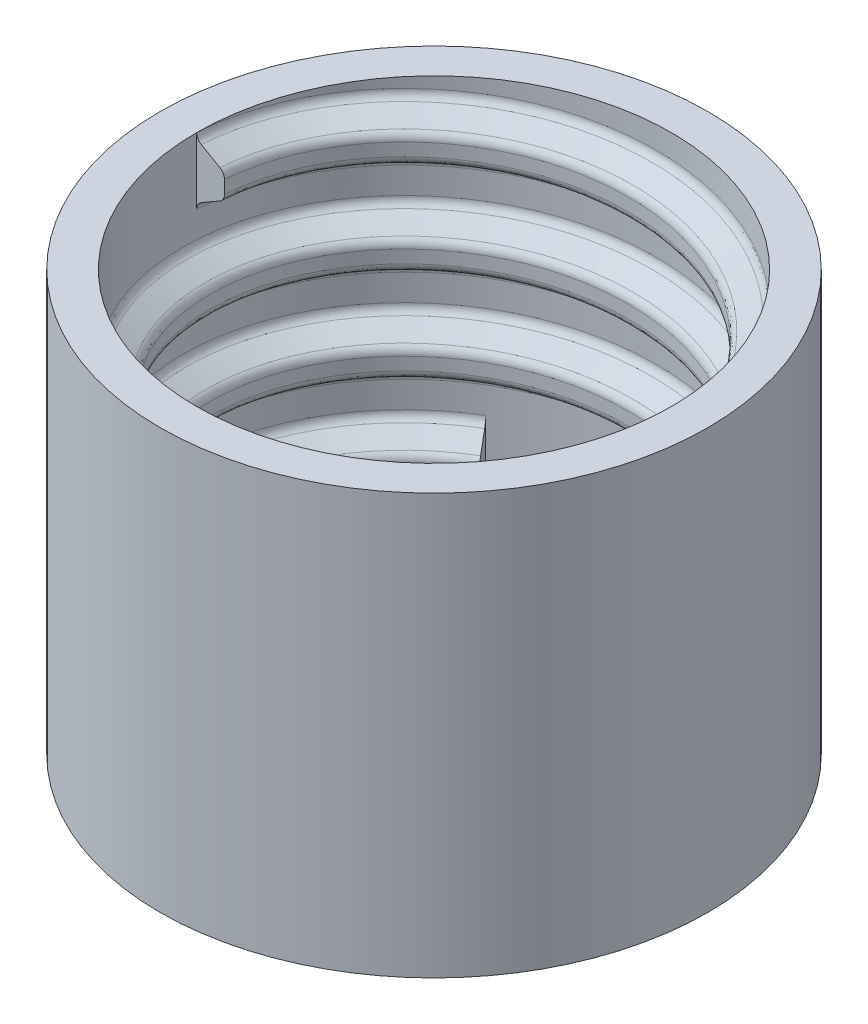
SolidWorks part; units mm, degrees
ref_plane "Front Plane" through (0, 0, 0) normal (0, 0, 1) x (1, 0, 0)
ref_plane "Top Plane" through (0, 0, 0) normal (0, 1, 0) x (1, 0, 0)
ref_plane "Right Plane" through (0, 0, 0) normal (1, 0, 0) x (0, 0, -1)
sketch "Sketch1" plane through (0, 0, 0) normal (0, 1, 0) x (1, 0, 0)
  circle A0 centre (0, 0) radius 15
extrude "Boss-Extrude1" add sketch "Sketch1" along normal blind 20 contours A0
sketch "Sketch2" plane through (0, 20, 0) normal (0, 1, 0) x (1, 0, 0)
  circle A0 centre (0, 0) radius 13
sketch "Sketch10" plane through (0, 20, 0) normal (0, 1, 0) x (1, 0, 0)
  circle A0 centre (0, 0) radius 13
extrude "Cut-Extrude2" cut sketch "Sketch10" against normal blind 20
thread "Thread1" pitch 5.08 method extrude profile "Thread Profile2" start angle 0, offset 0, length 16, pitch 5.08, diameter 26
ref_plane "Plane2" through (-13, 20, 0) normal (0, 0, -1) x (1, 0, 0)
sketch "Thread Profile2" plane through (-13, 20, 0) normal (0, 0, -1) x (1, 0, 0)
  line L0 (0, 0) -> (0, 5.08) construction
  line L1 (0, 0) -> (0, 3.6346)
  line L2 (0.508, 3.6346) -> (1.524, 3.6346) construction
  line L3 (1.524, 2.1681) -> (1.524, 1.4665)
  line L4 (1.27, 2.6081) -> (0.254, 3.1946)
  line L5 (1.27, 1.0265) -> (0.254, 0.4399)
  line L6 (0.508, 0) -> (1.524, 0) construction
  arc A0 (0.254, 3.1946) -> (0, 3.6346) centre (0.508, 3.6346) cw
  arc A1 (0.254, 0.4399) -> (0, 0) centre (0.508, 0) ccw
  arc A2 (1.524, 1.4665) -> (1.27, 1.0265) centre (1.016, 1.4665) cw
  arc A3 (1.524, 2.1681) -> (1.27, 2.6081) centre (1.016, 2.1681) ccw
  point P10 (1.524, 2.4614)
  point P17 (1.524, 1.1732)
  point P18 (0, 3.3413)
  point P19 (0, 0.2933)
  point P20 (0, 0)
  dimension "RootFillet1" = 0.508
  dimension "RootFillet2" = 0.508
  dimension "CrestFillet2" = 0.508
  dimension "CrestFillet1" = 0.508
  dimension "Pitch" = 5.08
  dimension "Angle1" = 30
  dimension "Angle2" = 30
  dimension "a" = 3.048
  dimension "b" = 1.524
  dimension "c" = 1.2882
sketch "Sketch19" plane through (0, 0, 0) normal (0, -1, 0) x (-1, 0, 0)
  circle A0 centre (0, 0) radius 13
  circle A1 centre (0, 0) radius 6.5
sketch "Sketch20" plane through (0, 0, 0) normal (0, -1, 0) x (1, 0, 0)
  circle A0 centre (0, 0) radius 15
extrude "Boss-Extrude3" add sketch "Sketch20" along normal blind 3
extrude "Cut-Extrude3" cut sketch "Sketch19" along normal blind 1.5 contours A1
sketch "Sketch47" plane through (0, -1.5, 0) normal (0, 1, 0) x (1, 0, 0)
  circle A0 centre (0, 0) radius 0.5
extrude "Cut-Extrude10" cut sketch "Sketch47" against normal blind 1.5
sketch "Sketch49" plane through (0, -1.5, 0) normal (0, 1, 0) x (1, 0, 0)
  circle A0 centre (0, 0) radius 0.5
  circle A2 centre (1.67, 0) radius 0.5
sketch "Sketch50" plane through (0, -1.5, 0) normal (0, 1, 0) x (1, 0, 0)
  circle A0 centre (3.33, 0) radius 0.5
sketch "Sketch51" plane through (0, -1.5, 0) normal (0, 1, 0) x (1, 0, 0)
  circle A0 centre (5, 0) radius 0.5
extrude "Cut-Extrude13" cut sketch "Sketch49" against normal blind 1.5
extrude "Cut-Extrude14" cut sketch "Sketch50" against normal blind 1.5
extrude "Cut-Extrude15" cut sketch "Sketch51" against normal blind 1.5
pattern_circular "CirPattern1" count 18 over 360 about axis through (0, -1.5, 0) along (0, 1, 0) of "Cut-Extrude15"
pattern_circular "CirPattern2" count 12 over 360 about axis through (0, -1.5, 0) along (0, 1, 0) of "Cut-Extrude14"
pattern_circular "CirPattern3" count 6 over 360 about axis through (0, -1.5, 0) along (0, 1, 0) of "Cut-Extrude13"
sketch "Sketch52" plane through (0, -3, 0) normal (0, -1, 0) x (-1, 0, 0)
  circle A0 centre (0, 0) radius 15
